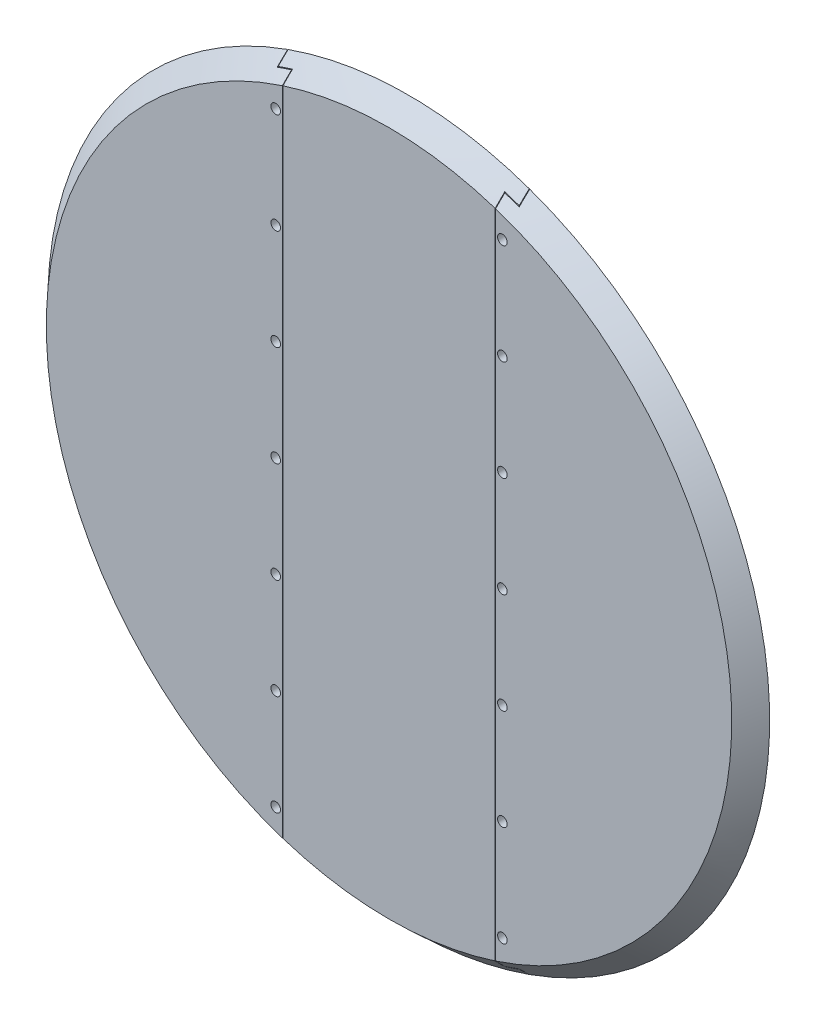
SolidWorks part; units mm, degrees
material "Stainless Steel 2205"
ref_plane "Front Plane" through (0, 0, 0) normal (0, 0, 1) x (1, 0, 0)
ref_plane "Top Plane" through (0, 0, 0) normal (0, 1, 0) x (1, 0, 0)
ref_plane "Right Plane" through (0, 0, 0) normal (1, 0, 0) x (0, 0, -1)
sketch "Sketch1" plane through (0, 0, 0) normal (0, 0, 1) x (1, 0, 0)
  circle A0 centre (0, 0) radius 1000
  dimension "D1" = 2000
extrude "Boss-Extrude2" add sketch "Sketch1" along normal blind 1
dome "Dome1" faces to dome 1 distance 1000 reverse direction no elliptical dome no face at (1000, 0, 1) parameters "D1"=1000
ref_plane "Plane1" through (0, 0, 1001) normal (0, 0, 1) x (1, 0, 0)
sketch "Sketch2" plane through (0, 0, 1001) normal (0, 0, 1) x (1, 0, 0)
  circle A0 centre (0, 0) radius 1000
  dimension "D1" = 2000
extrude "Cut-Extrude1" cut sketch "Sketch2" against normal blind 300
sketch "Sketch4" plane through (0, 0, 0) normal (0, 0, -1) x (-1, 0, 0)
  circle A0 centre (0, 0) radius 1000
extrude "Cut-Extrude2" cut sketch "Sketch4" against normal blind 660
sketch "Sketch6" plane through (0, 0, 0) normal (0, 1, 0) x (1, 0, 0)
  line L0 (-252.1429, -660) -> (-252.1429, -682)
  line L1 (752.1429, -660) -> (-752.1429, -660) construction
  line L2 (-252.1429, -682) -> (-222.1429, -682)
  line L3 (-222.1429, -682) -> (-222.1429, -701)
  line L4 (-714.1428, -701) -> (714.1428, -701) construction
  line L5 (-222.1429, -701) -> (-221.1429, -701)
  line L6 (-221.1429, -701) -> (-221.1429, -681)
  line L7 (-221.1429, -681) -> (-251.1429, -681)
  line L8 (-251.1429, -681) -> (-251.1429, -660)
  line L9 (252.1429, -660) -> (252.1429, -682)
  line L10 (252.1429, -682) -> (222.1429, -682)
  line L11 (222.1429, -682) -> (222.1429, -701)
  line L12 (222.1429, -701) -> (221.1429, -701)
  line L13 (221.1429, -701) -> (221.1429, -681)
  line L14 (221.1429, -681) -> (251.1429, -681)
  line L15 (251.1429, -681) -> (251.1429, -660)
  line L16 (251.1429, -660) -> (252.1429, -660)
  line L17 (-251.1429, -660) -> (-252.1429, -660)
  line L18 (-221.1429, -701) -> (-222.1429, -701)
  line L19 (252.1429, -660) -> (251.1429, -660)
  line L20 (222.1429, -701) -> (221.1429, -701)
  dimension "D1" = 1
  dimension "D2" = 1
  dimension "D3" = 1
  dimension "D4" = 30
  dimension "D5" = 20
  dimension "D6" = 500
  dimension "D7" = 1
  dimension "D8" = 1
  dimension "D9" = 1
  dimension "D10" = 30
  dimension "D11" = 20
  dimension "D12" = 500
extrude "Cut-Extrude5" cut sketch "Sketch6" against normal through all both and the other way through all contours L8 L17 L0 L2 L3 L5 L6 L7 | L16 L15 L14 L13 L12 L11 L10 L9 region at (-251.6429, 0, 660.514) region at (251.6289, 0, 671)
sketch "Sketch7" plane through (0, 0, 660) normal (0, 0, -1) x (-1, 0, 0)
  line L0 (-251.1429, 708.9755) -> (-251.1429, -708.9755) construction
  line L1 (251.1429, 708.9755) -> (251.1429, -708.9755) construction
  circle A0 centre (-236.1429, 0) radius 10
  circle A1 centre (-236.1429, 210) radius 10
  circle A2 centre (-236.1429, 420) radius 10
  circle A3 centre (-236.1429, 630) radius 10
  circle A4 centre (-236.1429, -210) radius 10
  circle A5 centre (-236.1429, -420) radius 10
  circle A6 centre (-236.1429, -630) radius 10
  circle A7 centre (236.1429, 0) radius 10
  circle A8 centre (236.1429, 210) radius 10
  circle A9 centre (236.1429, 420) radius 10
  circle A10 centre (236.1429, 630) radius 10
  circle A11 centre (236.1429, -210) radius 10
  circle A12 centre (236.1429, -420) radius 10
  circle A13 centre (236.1429, -630) radius 10
  point P32 (0, 0)
  dimension "D1" = 20
  dimension "D2" = 15
  dimension "D6" = 15
  dimension "D3" = 4
  dimension "D4" = 4
  dimension "D5" = 2
extrude "Cut-Extrude6" cut sketch "Sketch7" against normal through all both and the other way through all
